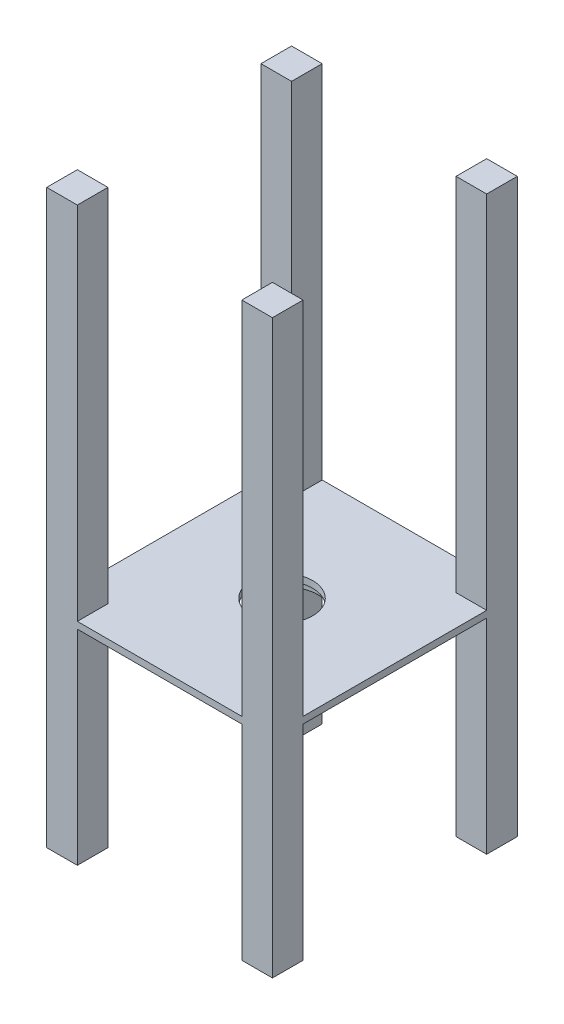
SolidWorks part; units mm, degrees
note: The reader was unsure of these and kept them because the rebuilt part matched: shared geometry of "Sketch1<11>", "Sketch1<12>", "Sketch1<13>", "Sketch1<14>".
material "Pine"
ref_plane "Front Plane" through (0, 0, 0) normal (0, 0, 1) x (1, 0, 0)
ref_plane "Top Plane" through (0, 0, 0) normal (0, 1, 0) x (1, 0, 0)
ref_plane "Right Plane" through (0, 0, 0) normal (1, 0, 0) x (0, 0, -1)
sketch "Sketch1" plane through (0, 0, 0) normal (0, 1, 0) x (1, 0, 0)
  line L0 (-187.325, 203.2) -> (-187.325, 152.4)
  line L1 (-187.325, -203.2) -> (187.325, -203.2)
  line L2 (-187.325, -203.2) -> (-187.325, 203.2)
  line L3 (-187.325, 203.2) -> (187.325, 203.2)
  line L4 (187.325, -203.2) -> (187.325, 203.2)
  line L5 (-187.325, -203.2) -> (187.325, 203.2) construction
  line L6 (-187.325, 203.2) -> (187.325, -203.2) construction
  line L7 (-187.325, 152.4) -> (-136.525, 152.4)
  line L8 (-136.525, 152.4) -> (-136.525, 203.2)
  line L9 (-136.525, 203.2) -> (-187.325, 203.2)
  line L10 (187.325, 203.2) -> (164.6437, 203.2)
  line L13 (187.325, 152.4) -> (187.325, 203.2)
  line L14 (136.525, 203.2) -> (136.525, 152.4)
  line L15 (136.525, 152.4) -> (187.325, 152.4)
  line L16 (187.325, 152.4) -> (187.325, 203.2)
  line L17 (187.325, 203.2) -> (136.525, 203.2)
  line L18 (136.525, -152.4) -> (136.525, -203.2)
  line L19 (136.525, -203.2) -> (187.325, -203.2)
  line L20 (187.325, -203.2) -> (187.325, -152.4)
  line L21 (187.325, -152.4) -> (136.525, -152.4)
  line L22 (-187.325, -152.4) -> (-187.325, -203.2)
  line L23 (-187.325, -203.2) -> (-136.525, -203.2)
  line L24 (-136.525, -203.2) -> (-136.525, -152.4)
  line L25 (-136.525, -152.4) -> (-187.325, -152.4)
  point P0 (0, 0)
  dimension "D1" = 374.65
  dimension "D2" = 406.4
  dimension "D3" = 50.8
  dimension "D4" = 50.8
  dimension "D5" = 50.8
  dimension "D6" = 50.8
  dimension "D7" = 50.8
  dimension "D8" = 50.8
  dimension "D9" = 50.8
  dimension "D10" = 50.8
extrude "Boss-Extrude2" add sketch "Sketch1" along normal blind 11.1125 contours L14 L15 L16 L17 | L2 L1 L4 L3 | L0 L7 L8 L9 | L24 L25 L22 L23 | L21 L18 L19 L20
extrude "Boss-Extrude3" add sketch "Sketch1<11>" along normal blind 609.6 contours L0 L7 L8 L9
sketch "Sketch1<11>" plane through (0, 0, 0) normal (0, 1, 0) x (1, 0, 0) same geometry as "Sketch1"
extrude "Boss-Extrude4" add sketch "Sketch1<12>" along normal blind 609.6 contours L25 L22 L23 L24
sketch "Sketch1<12>" plane through (0, 0, 0) normal (0, 1, 0) x (1, 0, 0) same geometry as "Sketch1"
extrude "Boss-Extrude5" add sketch "Sketch1<13>" along normal blind 609.6 contours L14 L15 L16 L17
sketch "Sketch1<13>" plane through (0, 0, 0) normal (0, 1, 0) x (1, 0, 0) same geometry as "Sketch1"
extrude "Boss-Extrude6" add sketch "Sketch1<14>" along normal blind 609.6 contours L21 L18 L19 L20
sketch "Sketch1<14>" plane through (0, 0, 0) normal (0, 1, 0) x (1, 0, 0) same geometry as "Sketch1"
sketch "Sketch4" plane through (0, 11.1125, 0) normal (0, 1, 0) x (1, 0, 0)
  circle A0 centre (0, 0) radius 50.8
  dimension "D1" = 101.6
extrude "Cut-Extrude2" cut sketch "Sketch4" against normal through all
sketch "Sketch5" plane through (0, 0, 0) normal (0, -1, 0) x (1, 0, 0)
  line L1 (-82.55, 76.2) -> (82.55, 76.2)
  line L2 (-82.55, 76.2) -> (-82.55, -76.2)
  line L3 (-82.55, -76.2) -> (82.55, -76.2)
  line L4 (82.55, 76.2) -> (82.55, -76.2)
  line L5 (-82.55, 76.2) -> (82.55, -76.2) construction
  line L6 (-82.55, -76.2) -> (82.55, 76.2) construction
  line L7 (-69.85, -63.5) -> (69.85, -63.5)
  line L8 (-69.85, -63.5) -> (-69.85, 63.5)
  line L9 (-69.85, 63.5) -> (69.85, 63.5)
  line L10 (69.85, -63.5) -> (69.85, 63.5)
  line L11 (-69.85, -63.5) -> (69.85, 63.5) construction
  line L12 (-69.85, 63.5) -> (69.85, -63.5) construction
  point P0 (0, 0)
  point P6 (0, 0)
  dimension "D1" = 152.4
  dimension "D2" = 165.1
  dimension "D3" = 139.7
  dimension "D4" = 127
extrude "Boss-Extrude8" add sketch "Sketch5" along normal blind 17.78 contours L8 L9 L10 L7 | L2 L3 L4 L1
sketch "Sketch11" plane through (0, -17.78, 0) normal (0, -1, 0) x (1, 0, 0)
  circle A0 centre (0, 0) radius 63.5 construction
sketch "Sketch13" plane through (0, 0, 0) normal (0, -1, 0) x (1, 0, 0)
  line L0 (-187.325, 203.2) -> (-187.325, 152.4)
  line L1 (-187.325, 152.4) -> (-136.525, 152.4)
  line L2 (-136.525, 152.4) -> (-136.525, 203.2)
  line L3 (-136.525, 203.2) -> (-187.325, 203.2)
  line L4 (136.525, 203.2) -> (187.325, 203.2)
  line L5 (187.325, 203.2) -> (187.325, 152.4)
  line L6 (187.325, 152.4) -> (136.525, 152.4)
  line L7 (136.525, 152.4) -> (136.525, 203.2)
  line L8 (187.325, -152.4) -> (136.525, -152.4)
  line L9 (136.525, -152.4) -> (136.525, -203.2)
  line L10 (136.525, -203.2) -> (187.325, -203.2)
  line L11 (187.325, -203.2) -> (187.325, -152.4)
  line L12 (-136.525, -152.4) -> (-187.325, -152.4)
  line L13 (-187.325, -152.4) -> (-187.325, -203.2)
  line L14 (-187.325, -203.2) -> (-136.525, -203.2)
  line L15 (-136.525, -203.2) -> (-136.525, -152.4)
sketch "Sketch14" plane through (0, 11.1125, 0) normal (0, 1, 0) x (1, 0, 0)
  circle A0 centre (0, 0) radius 55
  circle A1 centre (0, 0) radius 50.9026
  dimension "D1" = 110
extrude "Boss-Extrude13" add sketch "Sketch13" along normal blind 339.6
sketch "Sketch15" plane through (0, 0, 0) normal (0, -1, 0) x (1, 0, 0)
  circle A1 centre (0, 0) radius 63.5
  circle A2 centre (0, 0) radius 69.932
extrude "Boss-Extrude14" add sketch "Sketch15" along normal blind 17
